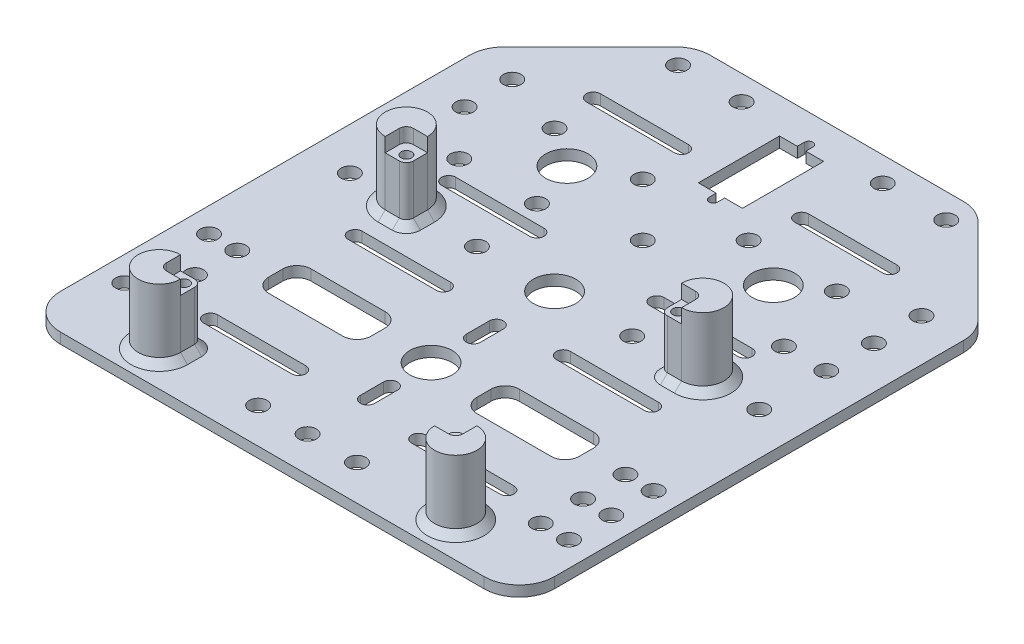
SolidWorks part; units mm, degrees
other "标注1"
sketch "草图9" plane through (140, 44, 0) normal (0.0097, 0.9564, 0.2917) x (0.944, 0.0875, -0.3181)
ref_plane "前视基准面" through (0, 0, 0) normal (0, 0, 1) x (1, 0, 0)
ref_plane "上视基准面" through (0, 0, 0) normal (0, 1, 0) x (1, 0, 0)
ref_plane "右视基准面" through (0, 0, 0) normal (1, 0, 0) x (0, 0, -1)
sketch "草图1" plane through (0, 0, 0) normal (0, 1, 0) x (1, 0, 0)
  line L1 (0, 0) -> (140, 0)
  line L2 (0, 0) -> (0, 160)
  line L3 (0, 160) -> (140, 160)
  line L4 (140, 0) -> (140, 160)
extrude "凸台-拉伸1" add sketch "草图1" along normal blind 4
sketch "草图2" plane through (0, 4, 0) normal (0, 1, 0) x (1, 0, 0)
  line L0 (-2.2, 0) -> (2.2, 0) construction
  line L1 (28, 24.5) -> (53, 24.5) construction
  line L2 (70, 120) -> (55, 120) construction
  line L3 (70, 120) -> (85, 120) construction
  line L4 (70, 112.5) -> (12, 112.5) construction
  line L5 (70, 112.5) -> (128, 112.5) construction
  line L6 (28, 133) -> (53, 133) construction
  line L7 (28, 26.5) -> (53, 26.5)
  line L8 (28, 22.5) -> (53, 22.5)
  line L9 (28, 92) -> (53, 92) construction
  line L10 (28, 94) -> (53, 94)
  line L11 (28, 90) -> (53, 90)
  line L12 (87, 24.5) -> (112, 24.5) construction
  line L15 (87, 92) -> (112, 92) construction
  line L16 (87, 94) -> (112, 94)
  line L17 (87, 90) -> (112, 90)
  line L18 (28, 135) -> (53, 135)
  line L19 (28, 131) -> (53, 131)
  line L20 (87, 26.5) -> (112, 26.5)
  line L23 (87, 133) -> (112, 133) construction
  line L24 (87, 135) -> (112, 135)
  line L25 (87, 131) -> (112, 131)
  line L26 (87, 22.5) -> (112, 22.5)
  line L51 (40.5, 65.5) -> (40.5, 24.5) construction
  line L56 (70, 63.5) -> (70, 57) construction
  line L57 (40.5, 51) -> (26, 51)
  line L58 (26, 51) -> (26, 39)
  line L59 (28, 65.5) -> (53, 65.5) construction
  line L60 (28, 67.5) -> (53, 67.5)
  line L61 (28, 63.5) -> (53, 63.5)
  line L62 (87, 65.5) -> (112, 65.5) construction
  line L63 (87, 67.5) -> (112, 67.5)
  line L64 (87, 63.5) -> (112, 63.5)
  line L65 (26, 39) -> (55, 39)
  line L66 (55, 39) -> (55, 51)
  line L67 (55, 51) -> (40.5, 51)
  line L68 (99.5, 51) -> (85, 51)
  line L69 (85, 51) -> (85, 39)
  line L70 (85, 39) -> (114, 39)
  line L71 (114, 39) -> (114, 51)
  line L72 (114, 51) -> (99.5, 51)
  line L73 (72, 63.5) -> (72, 57)
  line L74 (68, 63.5) -> (68, 57)
  line L75 (70, 33.5) -> (70, 27) construction
  line L76 (72, 33.5) -> (72, 27)
  line L77 (68, 33.5) -> (68, 27)
  line L245 (57.5, 92) -> (82.5, 92) construction
  line L246 (57.5, 94) -> (82.5, 94) [skipped]
  line L247 (57.5, 90) -> (82.5, 90) [skipped]
  line L248 (57.5, 92) -> (82.5, 92) construction
  line L249 (57.5, 94) -> (82.5, 94) [skipped]
  line L250 (57.5, 90) -> (82.5, 90) [skipped]
  circle A0 centre (55, 120) radius 2.5
  circle A1 centre (85, 120) radius 2.5
  circle A2 centre (12, 112.5) radius 2.5
  circle A3 centre (128, 112.5) radius 2.5
  circle A4 centre (12, 80) radius 2.5
  circle A5 centre (128, 80) radius 2.5
  arc A6 (28, 94) -> (28, 90) centre (28, 92) ccw
  arc A7 (53, 90) -> (53, 94) centre (53, 92) ccw
  arc A10 (87, 94) -> (87, 90) centre (87, 92) ccw
  arc A11 (112, 90) -> (112, 94) centre (112, 92) ccw
  arc A12 (28, 135) -> (28, 131) centre (28, 133) ccw
  arc A13 (53, 131) -> (53, 135) centre (53, 133) ccw
  arc A16 (87, 135) -> (87, 131) centre (87, 133) ccw
  arc A17 (112, 131) -> (112, 135) centre (112, 133) ccw
  circle A18 centre (7, 45.0804) radius 2.5
  circle A19 centre (15, 45.0804) radius 2.5
  circle A20 centre (15, 33.0804) radius 2.5
  circle A21 centre (15, 21.0804) radius 2.5
  circle A22 centre (7, 33.0804) radius 2.5
  circle A23 centre (7, 21.0804) radius 2.5
  circle A24 centre (133, 21.0804) radius 2.5
  circle A25 centre (133, 33.0804) radius 2.5
  circle A26 centre (125, 21.0804) radius 2.5
  circle A27 centre (125, 33.0804) radius 2.5
  circle A28 centre (125, 45.0804) radius 2.5
  circle A29 centre (133, 45.0804) radius 2.5
  circle A30 centre (70, 45) radius 6
  circle A32 centre (70, 80) radius 6
  circle A33 centre (12, 126) radius 2.5
  circle A34 centre (128, 126) radius 2.5
  circle A35 centre (70, 105) radius 2.5
  circle A36 centre (12, 99) radius 2.5
  circle A37 centre (128, 99) radius 2.5
  circle A38 centre (41, 112.5) radius 6
  circle A39 centre (99.5, 112.5) radius 6
  circle A40 centre (30, 120) radius 2.5
  circle A41 centre (110, 120) radius 2.5
  circle A42 centre (70, 10) radius 2.5
  circle A43 centre (56, 10) radius 2.5
  circle A44 centre (84, 10) radius 2.5
  arc A45 (28, 26.5) -> (28, 22.5) centre (28, 24.5) ccw
  arc A46 (53, 22.5) -> (53, 26.5) centre (53, 24.5) ccw
  arc A47 (87, 26.5) -> (87, 22.5) centre (87, 24.5) ccw
  arc A48 (112, 22.5) -> (112, 26.5) centre (112, 24.5) ccw
  arc A49 (28, 67.5) -> (28, 63.5) centre (28, 65.5) ccw
  arc A50 (53, 63.5) -> (53, 67.5) centre (53, 65.5) ccw
  arc A51 (87, 67.5) -> (87, 63.5) centre (87, 65.5) ccw
  arc A52 (112, 63.5) -> (112, 67.5) centre (112, 65.5) ccw
  circle A53 centre (48, 80) radius 2.5
  circle A54 centre (30, 80) radius 2.5
  circle A55 centre (92, 80) radius 2.5
  circle A56 centre (110, 80) radius 2.5
  arc A57 (72, 63.5) -> (68, 63.5) centre (70, 63.5) ccw
  arc A58 (68, 57) -> (72, 57) centre (70, 57) ccw
  arc A59 (72, 33.5) -> (68, 33.5) centre (70, 33.5) ccw
  arc A60 (68, 27) -> (72, 27) centre (70, 27) ccw
  arc A160 (57.5, 94) -> (57.5, 90) centre (57.5, 92) ccw [skipped]
  arc A161 (82.5, 90) -> (82.5, 94) centre (82.5, 92) ccw [skipped]
  point P0 (70, 80)
  point P1 (12, 126)
  point P2 (70, 0)
  point P3 (70, 120)
  point P16 (70, 0)
  point P21 (70, 45)
  point P24 (45, 105)
  point P27 (40.5, 92)
  point P33 (40.5, 133)
  point P34 (128, 126)
  point P40 (70, 105)
  point P41 (12, 99)
  point P43 (99.5, 92)
  point P57 (40.5, 112.5)
  point P61 (99.5, 133)
  point P67 (7, 45.0804)
  point P92 (133, 45.0804)
  point P93 (70, 63.5)
  point P98 (40.5, 45)
  point P100 (48, 80)
  point P101 (70, 105)
  point P106 (30, 80)
  point P111 (30, 120)
  point P120 (70, 10)
  point P121 (56, 10)
  point P128 (92, 80)
  point P129 (110, 80)
  point P134 (70, 60.25)
  point P137 (70, 57)
  point P142 (84, 10)
  point P143 (70, 105)
  point P150 (70, 105)
  point P151 (40.5, 24.5)
  point P157 (70, 105)
  point P158 (40.5, 65.5)
  point P161 (99.5, 24.5)
  point P164 (70, 105)
  point P171 (70, 105)
  point P174 (99.5, 65.5)
  point P178 (70, 105)
  point P182 (70, 33.5)
  point P183 (70, 30.25)
  point P185 (70, 105)
  point P187 (70, 27)
  point P192 (70, 105)
  point P199 (70, 105)
  point P206 (70, 75)
  point P213 (70, 75)
  point P220 (70, 84)
  point P227 (70, 84)
  point P234 (70, 84)
  point P241 (70, 84)
  point P248 (70, 92)
  point P255 (70, 92)
  point P262 (70.0958, 92)
  point P269 (70.0958, 92)
  point P276 (70.0958, 92)
  point P283 (70.0958, 92)
  point P290 (70, 92)
  point P297 (70, 92)
  point P304 (70, 92)
  point P311 (70, 92)
  point P318 (70, 92)
  point P325 (70, 92)
  point P332 (70, 92)
  point P339 (70, 92)
  point P346 (70, 92)
  point P353 (70, 92)
  point P360 (70, 92)
  point P367 (70, 92)
  point P374 (70, 92)
  point P381 (70, 92)
  point P388 (70, 92)
  point P395 (70, 92)
  point P402 (70, 92)
  point P409 (70, 92)
  point P416 (70, 92)
  point P423 (70, 92)
  point P430 (70, 92)
  point P437 (70, 92)
  point P444 (70, 92)
  point P451 (70, 92)
  point P458 (70, 92)
  point P465 (70, 92)
  point P472 (70, 92)
  point P479 (70, 92)
  point P486 (70, 92)
  point P493 (70, 92)
  point P500 (70, 92)
  point P507 (70, 92)
  point P514 (70, 92)
  point P521 (70, 92)
  point P528 (70, 92)
  point P535 (70, 92)
  point P542 (70, 92)
  point P549 (70, 92)
  point P556 (70, 92)
  point P563 (70, 92)
  point P570 (70, 92)
  point P577 (70, 92)
  point P584 (70, 92)
  dimension "D1" = 3
  dimension "D2" = 2
  dimension "D4" = 2
  dimension "D3" = 3
extrude "切除-拉伸1" cut sketch "草图2" against normal through all
sketch "草图4" plane through (0, 4, 0) normal (0, 1, 0) x (1, 0, 0)
  line L7 (70, 80) -> (70, 10) construction
  line L9 (28, 80) -> (112, 80)
  line L10 (28, 80) -> (28, 10)
  line L11 (28, 10) -> (112, 10)
  line L12 (112, 80) -> (112, 10)
  line L13 (28, 74) -> (34, 74)
  line L15 (34, 80) -> (34, 74)
  line L17 (106, 80) -> (106, 74)
  line L18 (106, 74) -> (112, 74)
  line L20 (28, 16) -> (34, 16)
  line L21 (34, 16) -> (34, 10)
  line L22 (112, 16) -> (106, 16)
  line L23 (106, 16) -> (106, 10)
  circle A1 centre (28, 80) radius 6
  circle A2 centre (112, 80) radius 6
  circle A3 centre (28, 10) radius 6
  circle A4 centre (112, 10) radius 6
extrude "凸台-拉伸3" add sketch "草图4" along normal blind 20 contours L9 A1 L10 | L10 A1 L9 | L12 A2 L9 | L9 A2 L12 | L11 A4 L12 | L12 A4 L11 | L10 A3 L11 | L11 A3 L10 | A1 L13 L15 | A2 L17 L18 | A4 L22 L23 | A3 L21 L20 region at (27.1512, 4, -80.8488) region at (30.5465, 4, -77.4535) region at (32.6598, 4, -75.3402) region at (112.8488, 4, -80.8488) region at (107.3402, 4, -75.3402) region at (109.4535, 4, -77.4535) region at (30.5465, 4, -12.5465) region at (32.6598, 4, -14.6598) region at (27.1512, 4, -9.1512) region at (112.8488, 4, -9.1512) region at (107.3402, 4, -14.6598) region at (109.4535, 4, -12.5465)
extrude "切除-拉伸2" cut sketch "草图4<4>" against normal blind 4 from surface contours L10 A1 L9 | L9 A2 L12 | L12 A4 L11 | L11 A3 L10 | A1 L13 L15 | A3 L21 L20 | A4 L22 L23 | A2 L17 L18 region at (30.5465, 4, -77.4535) region at (32.6598, 4, -75.3402) region at (107.3402, 4, -75.3402) region at (109.4535, 4, -77.4535) region at (30.5465, 4, -12.5465) region at (32.6598, 4, -14.6598) region at (107.3402, 4, -14.6598) region at (109.4535, 4, -12.5465) starting at face at (29.5858, 24, -78.4142)
sketch "草图4<4>" plane through (0, 4, 0) normal (0, 1, 0) x (1, 0, 0) same geometry as "草图4"
sketch "草图5" plane through (0, 4, 0) normal (0, 1, 0) x (1, 0, 0)
  line L0 (70, 100) -> (70, 96.0804) construction
  line L1 (63.75, 150) -> (76.25, 150)
  line L2 (63.75, 150) -> (63.75, 127)
  line L3 (63.75, 127) -> (76.25, 127)
  line L4 (76.25, 150) -> (76.25, 127)
  point P0 (70, 100)
fillet "圆角2" radius 2 4 edges at (28, 22, -10) (112, 22, -10) (112, 22, -80) (28, 22, -80)
sketch "草图8" plane through (0, 20, 0) normal (0, 1, 0) x (1, 0, 0)
  line L0 (106, 10) -> (110, 10) construction
  line L1 (112, 12) -> (112, 16) construction
  line L2 (112, 16) -> (106, 16) construction
  line L3 (106, 16) -> (106, 10) construction
  line L4 (28, 16) -> (28, 12) construction
  line L5 (30, 10) -> (34, 10) construction
  line L6 (34, 10) -> (34, 16) construction
  line L7 (34, 16) -> (28, 16) construction
  line L8 (34, 80) -> (30, 80) construction
  line L9 (28, 78) -> (28, 74) construction
  line L10 (28, 74) -> (34, 74) construction
  line L11 (34, 74) -> (34, 80) construction
  line L12 (112, 74) -> (112, 78) construction
  line L13 (110, 80) -> (106, 80) construction
  line L14 (106, 80) -> (106, 74) construction
  line L15 (106, 74) -> (112, 74) construction
  line L16 (106, 10) -> (110, 10)
  line L17 (112, 12) -> (112, 16)
  line L18 (112, 16) -> (106, 16)
  line L19 (106, 16) -> (106, 10)
  line L20 (28, 16) -> (28, 12)
  line L21 (30, 10) -> (34, 10)
  line L22 (34, 10) -> (34, 16)
  line L23 (34, 16) -> (28, 16)
  line L24 (34, 80) -> (30, 80)
  line L25 (28, 78) -> (28, 74)
  line L26 (28, 74) -> (34, 74)
  line L27 (34, 74) -> (34, 80)
  line L28 (112, 74) -> (112, 78)
  line L29 (110, 80) -> (106, 80)
  line L30 (106, 80) -> (106, 74)
  line L31 (106, 74) -> (112, 74)
  arc A0 (110, 10) -> (112, 12) centre (110, 12) ccw construction
  arc A1 (28, 12) -> (30, 10) centre (30, 12) ccw construction
  arc A2 (30, 80) -> (28, 78) centre (30, 78) ccw construction
  arc A3 (112, 78) -> (110, 80) centre (110, 78) ccw construction
  arc A4 (110, 10) -> (112, 12) centre (110, 12) ccw
  arc A5 (28, 12) -> (30, 10) centre (30, 12) ccw
  arc A6 (30, 80) -> (28, 78) centre (30, 78) ccw
  arc A7 (112, 78) -> (110, 80) centre (110, 78) ccw
  circle A8 centre (31.5, 76.5) radius 1.5
  circle A9 centre (108.5, 76.5) radius 1.5
  circle A10 centre (108.5, 13.5) radius 1.5
  circle A11 centre (31.5, 13.5) radius 1.5
  point P3 (31.5, 76.5)
  dimension "D1" = 2
  dimension "D2" = 2
extrude "切除-拉伸4" cut sketch "草图8" against normal blind 4 contours A11 | A9 | A8 | A10 region at (31.5, 20, -76.5) region at (108.5, 20, -76.5) region at (108.5, 20, -13.5) region at (31.5, 20, -13.5)
fillet "圆角3" radius 2 4 edges at (106, 12, -16) (34, 12, -16) (106, 12, -74) (34, 12, -74)
chamfer "倒角5" distance 2 angle 45 16 edges at (33.4142, 4, -74.5858) (34, 4, -78) (30, 4, -74) (106.5858, 4, -74.5858) (110, 4, -74) (106, 4, -78) (106.5858, 4, -15.4142) (106, 4, -12) (110, 4, -16) (116.2426, 4, -5.7574) (33.4142, 4, -15.4142) (30, 4, -16) (34, 4, -12) (23.7574, 4, -5.7574) (23.7574, 4, -84.2426) (116.2426, 4, -84.2426)
sketch "草图11" plane through (0, 4, 0) normal (0, 1, 0) x (1, 0, 0)
  line L1 (68.8, 152) -> (68.8, 125)
  line L2 (71.2, 152) -> (71.2, 125)
  circle A0 centre (70, 152) radius 1.2
  circle A1 centre (70, 125) radius 1.2
  point P0 (70, 152)
extrude "切除-拉伸6" cut sketch "草图1<2>" along normal blind 1
sketch "草图1<2>" plane through (0, 0, 0) normal (0, 1, 0) x (1, 0, 0) same geometry as "草图1"
sketch "草图14" plane through (0, 4, 0) normal (0, 1, 0) x (1, 0, 0)
  circle A1 centre (32, 153) radius 2.5
  circle A2 centre (108, 153) radius 2.5
  circle A8 centre (50, 153) radius 2.5
  circle A10 centre (90, 153) radius 2.5
  circle A15 centre (116, 99) radius 2.5
  circle A16 centre (94, 99) radius 2.5
  circle A17 centre (46, 99) radius 2.5
  circle A18 centre (24, 99) radius 2.5
  point P0 (50, 153)
  point P1 (70, 153)
  point P4 (90, 153)
chamfer "倒角6" distance 30 angle 45 2 edges at (140, 2.5, -160) (0, 2.5, -160)
extrude "切除-拉伸8" cut sketch "草图5" against normal through all
extrude "切除-拉伸9" cut sketch "草图14" against normal through all
fillet "圆角4" radius 4 8 edges at (114, 2.5, -39) (85, 2.5, -39) (85, 2.5, -51) (114, 2.5, -51) (26, 2.5, -39) (55, 2.5, -39) (55, 2.5, -51) (26, 2.5, -51)
fillet "圆角5" radius 10 6 edges at (0, 2.5, 0) (140, 2.5, 0) (140, 2.5, -130) (0, 2.5, -130) (30, 2.5, -160) (110, 2.5, -160)
extrude "切除-拉伸10" cut sketch "草图11" against normal through all contours A1 L2 A0 L1 | A1 | A0 region at (70, 4, -138.5) region at (70, 4, -125)
